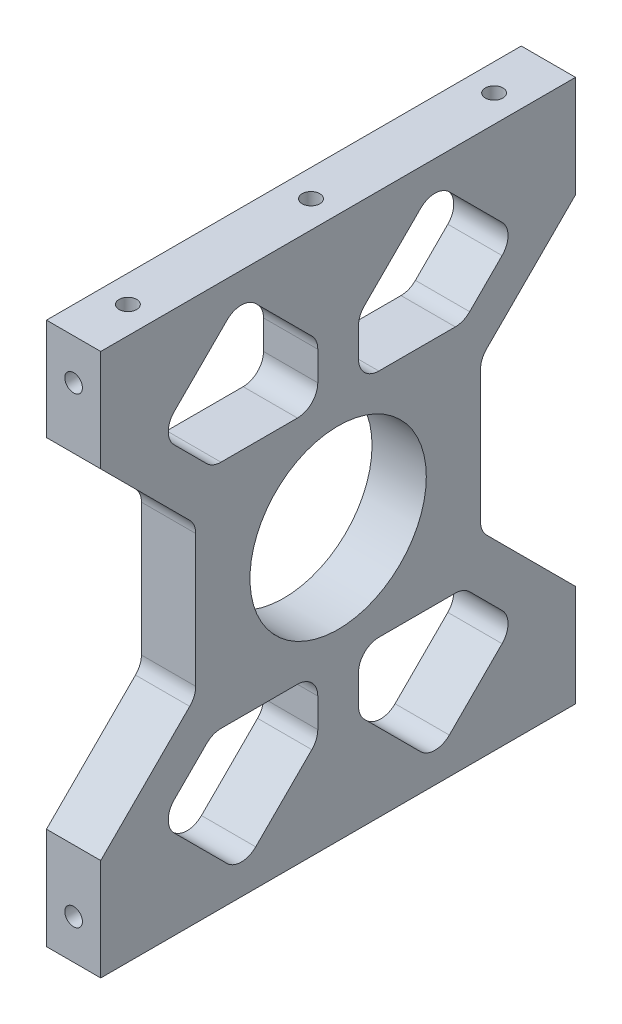
SolidWorks part; units mm, degrees
material "AISI 304"
ref_plane "前视基准面" through (0, 0, 0) normal (0, 0, 1) x (1, 0, 0)
ref_plane "上视基准面" through (0, 0, 0) normal (0, 1, 0) x (1, 0, 0)
ref_plane "右视基准面" through (0, 0, 0) normal (1, 0, 0) x (0, 0, -1)
sketch "草图1" plane through (0, 0, 0) normal (1, 0, 0) x (0, 0, -1)
  line L1 (-35, 40) -> (35, 40)
  line L2 (-35, 40) -> (-35, -40)
  line L3 (-35, -40) -> (35, -40)
  line L4 (35, 40) -> (35, -40)
  line L5 (-35, 40) -> (35, -40) construction
  line L6 (-35, -40) -> (35, 40) construction
  point P0 (0, 0)
  dimension "D1" = 80
  dimension "D2" = 70
extrude "凸台-拉伸1" add sketch "草图1" along normal blind 8
sketch "草图4" plane through (8, 0, 0) normal (1, 0, 0) x (0, 0, -1)
  circle A0 centre (0, 0) radius 13
  dimension "D1" = 26
extrude "切除-拉伸2" cut sketch "草图4" against normal blind 8
sketch "草图5" plane through (0, 0, 35) normal (0, 0, 1) x (1, 0, 0)
  circle A0 centre (4, 34) radius 1.3
  circle A1 centre (4, -34.1568) radius 1.3
  dimension "D1" = 2.6
  dimension "D2" = 2.6
extrude "切除-拉伸3" cut sketch "草图5" against normal blind 10
mirror "镜向1" about plane through (0, 0, 0) normal (0, 0, 1) of "切除-拉伸3"
sketch "草图6" plane through (0, 40, 0) normal (0, 1, 0) x (1, 0, 0)
  line L0 (8, 35) -> (8, -35) construction
  line L1 (8, 35) -> (0, 35) construction
  line L2 (8, -35) -> (0, -35) construction
  circle A0 centre (4, 27) radius 1.3
  circle A1 centre (4, -27) radius 1.3
  circle A2 centre (4, 0) radius 1.3
  dimension "D1" = 2.6
  dimension "D2" = 4
  dimension "D3" = 4
  dimension "D4" = 4
  dimension "D5" = 8
  dimension "D6" = 8
  dimension "D7" = 35
extrude "切除-拉伸4" cut sketch "草图6" against normal blind 10
mirror "镜向2" about plane through (0, 0, 0) normal (0, 1, 0) of "切除-拉伸4"
sketch "草图7" plane through (0, 0, 0) normal (-1, 0, 0) x (0, 0, 1)
  line L0 (0, 0) -> (0, 30.3391) construction
  line L1 (30.7136, 0) -> (-30.7136, 0) construction
  line L2 (-35, 25) -> (-21.8787, 11.8787)
  line L3 (-35, -40) -> (-35, 40) construction
  line L4 (-21, 9.7574) -> (-21, -9.7574)
  line L5 (-21.8787, -11.8787) -> (-35, -25)
  line L6 (-35, 25) -> (-35, -25)
  line L7 (35, 25) -> (35, -25)
  line L8 (21.8787, -11.8787) -> (35, -25)
  line L9 (21, 9.7574) -> (21, -9.7574)
  line L10 (35, 25) -> (21.8787, 11.8787)
  line L11 (-16.3934, 34.6777) -> (-24.1716, 26.8995)
  line L12 (-24.1716, 22.6569) -> (-19.3934, 17.8787)
  line L13 (-17.2721, 17) -> (-6, 17)
  line L14 (-3, 20) -> (-3, 24.2843)
  line L15 (-3.8787, 26.4056) -> (-12.1508, 34.6777)
  line L16 (-3.8787, -26.4056) -> (-12.1508, -34.6777)
  line L17 (-3, -20) -> (-3, -24.2843)
  line L18 (-17.2721, -17) -> (-6, -17)
  line L19 (-24.1716, -22.6569) -> (-19.3934, -17.8787)
  line L20 (-16.3934, -34.6777) -> (-24.1716, -26.8995)
  line L21 (16.3934, -34.6777) -> (24.1716, -26.8995)
  line L22 (24.1716, -22.6569) -> (19.3934, -17.8787)
  line L23 (17.2721, -17) -> (6, -17)
  line L24 (3, -20) -> (3, -24.2843)
  line L25 (3.8787, -26.4056) -> (12.1508, -34.6777)
  line L26 (3.8787, 26.4056) -> (12.1508, 34.6777)
  line L27 (3, 20) -> (3, 24.2843)
  line L28 (17.2721, 17) -> (6, 17)
  line L29 (24.1716, 22.6569) -> (19.3934, 17.8787)
  line L30 (16.3934, 34.6777) -> (24.1716, 26.8995)
  circle A0 centre (0, 0) radius 13 construction
  arc A1 (21.8787, -11.8787) -> (21, -9.7574) centre (24, -9.7574) cw
  arc A2 (21, 9.7574) -> (21.8787, 11.8787) centre (24, 9.7574) cw
  arc A3 (-21, -9.7574) -> (-21.8787, -11.8787) centre (-24, -9.7574) cw
  arc A4 (-21.8787, 11.8787) -> (-21, 9.7574) centre (-24, 9.7574) cw
  arc A5 (-24.1716, 26.8995) -> (-24.1716, 22.6569) centre (-22.0503, 24.7782) ccw
  arc A6 (-19.3934, 17.8787) -> (-17.2721, 17) centre (-17.2721, 20) ccw
  arc A7 (-6, 17) -> (-3, 20) centre (-6, 20) ccw
  arc A8 (-3, 24.2843) -> (-3.8787, 26.4056) centre (-6, 24.2843) ccw
  arc A9 (-16.3934, 34.6777) -> (-12.1508, 34.6777) centre (-14.2721, 32.5563) cw
  arc A10 (-16.3934, -34.6777) -> (-12.1508, -34.6777) centre (-14.2721, -32.5563) ccw
  arc A11 (-3, -24.2843) -> (-3.8787, -26.4056) centre (-6, -24.2843) cw
  arc A12 (-6, -17) -> (-3, -20) centre (-6, -20) cw
  arc A13 (-19.3934, -17.8787) -> (-17.2721, -17) centre (-17.2721, -20) cw
  arc A14 (-24.1716, -26.8995) -> (-24.1716, -22.6569) centre (-22.0503, -24.7782) cw
  arc A15 (24.1716, -26.8995) -> (24.1716, -22.6569) centre (22.0503, -24.7782) ccw
  arc A16 (19.3934, -17.8787) -> (17.2721, -17) centre (17.2721, -20) ccw
  arc A17 (6, -17) -> (3, -20) centre (6, -20) ccw
  arc A18 (3, -24.2843) -> (3.8787, -26.4056) centre (6, -24.2843) ccw
  arc A19 (16.3934, -34.6777) -> (12.1508, -34.6777) centre (14.2721, -32.5563) cw
  arc A20 (16.3934, 34.6777) -> (12.1508, 34.6777) centre (14.2721, 32.5563) ccw
  arc A21 (3, 24.2843) -> (3.8787, 26.4056) centre (6, 24.2843) cw
  arc A22 (6, 17) -> (3, 20) centre (6, 20) cw
  arc A23 (19.3934, 17.8787) -> (17.2721, 17) centre (17.2721, 20) cw
  arc A24 (24.1716, 26.8995) -> (24.1716, 22.6569) centre (22.0503, 24.7782) cw
  arc A25 (21.8787, 11.8787) -> (21, 9.7574) centre (24, 9.7574) ccw
  arc A26 (21, -9.7574) -> (21.8787, -11.8787) centre (24, -9.7574) ccw
  point P17 (21, -11)
  point P20 (21, 11)
  point P23 (-21, -11)
  point P26 (-21, 11)
  point P35 (-26.2929, 24.7782)
  point P38 (-18.5147, 17)
  point P45 (-14.2721, 36.799)
  point P61 (-14.2721, -36.799)
  point P62 (-18.5147, -17)
  point P63 (-26.2929, -24.7782)
  point P95 (26.2929, -24.7782)
  point P96 (18.5147, -17)
  point P97 (14.2721, -36.799)
  point P98 (14.2721, 36.799)
  point P99 (18.5147, 17)
  point P100 (26.2929, 24.7782)
  line M34 (-35, 40) -> (-35, -40)
  line M36 (35, -40) -> (35, 40)
  dimension "D6" = 3
  dimension "D12" = 3
  dimension "D1" = 14
  dimension "D2" = 45
  dimension "D3" = 45
  dimension "D4" = 25
  dimension "D5" = 25
  dimension "D7" = 6
  dimension "D8" = 17
  dimension "D9" = 3
  dimension "D10" = 11
  dimension "D11" = 17
extrude "切除-拉伸5" cut sketch "草图7" against normal blind 10 contours A9 L11 A5 L12 A6 L13 A7 L14 A8 L15 | A24 L30 A20 L26 A21 L27 A22 L28 A23 L29 | A2 L9 A1 L8 L10 M36 | A4 L2 L5 A3 L4 M34 | A14 L20 A10 L16 A11 L17 A12 L18 A13 L19 | A19 L21 A15 L22 A16 L23 A17 L24 A18 L25 region at (0, 0, -28.9133) region at (0, 0, 28.9133) region at (0, 24.8642, -13.5325) region at (0, -24.8642, -13.5325) region at (0, -24.8642, 13.5325) region at (0, 24.8642, 13.5325)
